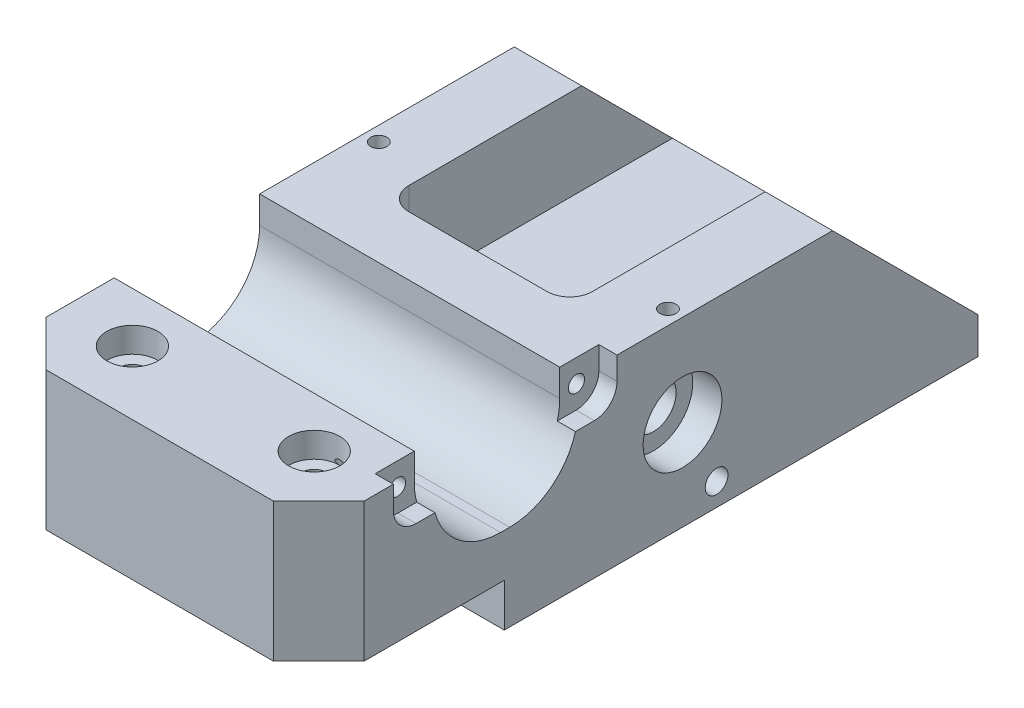
SolidWorks part; units mm, degrees
material "Nylon 6/10"
ref_plane "Front Plane" through (0, 0, 0) normal (0, 0, 1) x (1, 0, 0)
ref_plane "Top Plane" through (0, 0, 0) normal (0, 1, 0) x (1, 0, 0)
ref_plane "Right Plane" through (0, 0, 0) normal (1, 0, 0) x (0, 0, -1)
sketch "Sketch1" plane through (0, 0, 0) normal (0, 1, 0) x (1, 0, 0)
  line L1 (-22.225, -46.0375) -> (22.225, -46.0375)
  line L2 (-22.225, -46.0375) -> (-22.225, 46.0375)
  line L3 (-22.225, 46.0375) -> (22.225, 46.0375)
  line L4 (22.225, -46.0375) -> (22.225, 46.0375)
  line L5 (-22.225, -46.0375) -> (22.225, 46.0375) construction
  line L6 (-22.225, 46.0375) -> (22.225, -46.0375) construction
  point P0 (0, 0)
  dimension "D1" = 44.45
  dimension "D2" = 92.075
extrude "Base" add sketch "Sketch1" along normal blind 12.7 and the other way blind 12.7
sketch "Sketch2" plane through (0, 0, -46.0375) normal (0, 0, -1) x (-1, 0, 0)
  line L1 (-22.225, -12.7) -> (22.225, -12.7) construction
  circle A0 centre (0, -12.7) radius 4.7625
  dimension "D1" = 9.525
extrude "ShaftGuide" cut sketch "Sketch2" against normal blind 41.275
ref_plane "Plane1" through (0, -12.7, 0) normal (0, -1, 0) x (-1, 0, 0)
sketch "Sketch3" plane through (0, -12.7, 0) normal (0, -1, 0) x (-1, 0, 0)
  line L0 (10.922, -20.1295) -> (16.002, -20.1295)
  line L1 (22.225, -46.0375) -> (-22.225, -46.0375) construction
  line L2 (-22.225, -46.0375) -> (-22.225, 46.0375) construction
  line L3 (0, 0) -> (0, 102.0916) construction
  line L5 (-10.922, -20.1295) -> (-10.922, -3.3655)
  line L6 (-22.225, -46.0375) -> (22.225, -46.0375)
  line L7 (-10.922, -3.3655) -> (10.922, -3.3655)
  line L8 (10.922, -20.1295) -> (10.922, -3.3655)
  line L10 (-10.922, -20.1295) -> (-22.225, -20.1295)
  line L11 (-22.225, -46.0375) -> (-22.225, -20.1295)
  line L13 (22.225, -46.0375) -> (22.225, -20.1295)
  line L14 (4.7625, 46.0375) -> (4.7625, 4.7625)
  line L15 (4.7625, 4.7625) -> (-4.7625, 4.7625)
  line L16 (-4.7625, 4.7625) -> (-4.7625, 46.0375)
  line L17 (-4.7625, 46.0375) -> (-22.225, 46.0375)
  line L18 (-22.225, 46.0375) -> (-22.225, -46.0375)
  line L19 (-22.225, -46.0375) -> (22.225, -46.0375)
  line L20 (22.225, -46.0375) -> (22.225, 46.0375)
  line L21 (22.225, 46.0375) -> (4.7625, 46.0375)
  line L23 (22.225, 46.0375) -> (22.225, -46.0375) construction
  line L25 (-4.7625, 46.0375) -> (-22.225, 46.0375) construction
  line L26 (22.225, -20.1295) -> (16.002, -20.1295)
  line L28 (22.225, -46.0375) -> (22.225, 46.0375) construction
  line L29 (22.225, 46.0375) -> (4.7625, 46.0375) construction
  dimension "D6" = 21.844
  dimension "D3" = 49.403
  dimension "D7" = 16.764
  dimension "D1" = 0
extrude "ActuatorPlaneCut" cut sketch "Sketch3" against normal blind 6.0325
sketch "Sketch5" plane through (0, 0, 0) normal (0, 1, 0) x (1, 0, 0)
  line L1 (12.827, 11.1125) -> (-12.827, 11.1125)
  line L2 (12.827, -1.5875) -> (12.827, 11.1125)
  line L3 (12.827, -1.5875) -> (-12.827, -1.5875)
  line L4 (0, 0) -> (0, 121.8983) construction
  line L5 (-10.922, -3.3655) -> (10.922, -3.3655) construction
  line L6 (-12.827, -1.5875) -> (-12.827, 11.1125)
  point P17 (12.827, -1.5875)
  point P20 (12.827, 11.1125)
  dimension "D3" = 1.778
  dimension "D1" = 12.7
  dimension "D2" = 25.654
extrude "CenterSlot" cut sketch "Sketch5" along normal through all and the other way through all
fillet "CenterSlotFillet" radius 3.175 4 edges at (-12.827, 0, -11.1125) (-12.827, 0, 1.5875) (12.827, 0, 1.5875) (12.827, 0, -11.1125)
sketch "Sketch40" plane through (0, -12.7, 0) normal (0, -1, 0) x (1, 0, 0)
  line L1 (10.922, -0.9525) -> (-10.922, -0.9525)
  line L2 (10.922, -0.9525) -> (10.922, 16.9545)
  line L3 (7.747, 20.1295) -> (-7.747, 20.1295)
  line L4 (-10.922, -0.9525) -> (-10.922, 16.9545)
  line L6 (10.922, 3.3655) -> (10.922, 20.1295) construction
  line L7 (-9.652, 1.5875) -> (9.652, 1.5875) construction
  arc A0 (-7.747, 20.1295) -> (-10.922, 16.9545) centre (-7.747, 16.9545) ccw
  arc A1 (7.747, 20.1295) -> (10.922, 16.9545) centre (7.747, 16.9545) cw
  point P8 (-10.922, 20.1295)
  dimension "D1" = 3.175
  dimension "D2" = 2.54
extrude "GearBoxPit" cut sketch "Sketch40" against normal blind 11.176
sketch "Sketch60" plane through (0, 12.7, 0) normal (0, 1, 0) x (1, 0, 0)
  line L0 (22.225, 46.0375) -> (-22.225, 46.0375) construction
  line L1 (-12.827, 7.9375) -> (12.827, 7.9375)
  line L2 (-12.827, 7.9375) -> (-12.827, 46.0375)
  line L3 (-12.827, 46.0375) -> (12.827, 46.0375)
  line L4 (12.827, 7.9375) -> (12.827, 46.0375)
  line L5 (12.827, 1.5875) -> (12.827, 7.9375) construction
extrude "FrontCutaway" cut sketch "Sketch60" against normal blind 12.7
chamfer "ChamferFront" distance 20.32 angle 45 2 edges at (-17.526, 12.7, -46.0375) (17.526, 12.7, -46.0375)
sketch "Sketch67" plane through (0, -12.7, 0) normal (0, -1, 0) x (-1, 0, 0)
  line L0 (-12.3825, -5.3975) -> (12.3825, -5.3975) construction
  line L1 (-12.3825, -5.0006) -> (12.3825, -5.0006)
  line L2 (-12.3825, -5.7944) -> (12.3825, -5.7944)
  line L3 (-12.3825, -16.0655) -> (12.3825, -16.0655) construction
  line L4 (-12.3825, -15.6686) -> (12.3825, -15.6686)
  line L5 (-12.3825, -16.4624) -> (12.3825, -16.4624)
  line L6 (9.652, -1.5875) -> (-9.652, -1.5875) construction
  line L7 (0, 0.0055) -> (0, 0.7987) construction
  arc A0 (-12.3825, -5.0006) -> (-12.3825, -5.7944) centre (-12.3825, -5.3975) ccw
  arc A1 (12.3825, -5.7944) -> (12.3825, -5.0006) centre (12.3825, -5.3975) ccw
  arc A2 (-12.3825, -15.6686) -> (-12.3825, -16.4624) centre (-12.3825, -16.0655) ccw
  arc A3 (12.3825, -16.4624) -> (12.3825, -15.6686) centre (12.3825, -16.0655) ccw
  point P2 (0, -5.3975)
  point P9 (0, -16.0655)
  dimension "D1" = 0.7937
  dimension "D2" = 3.81
  dimension "D3" = 24.765
  dimension "D4" = 10.668
extrude "GearBoxSlotsH" cut sketch "Sketch67" against normal blind 2.286
sketch "Sketch55" plane through (-22.225, 0, 0) normal (-1, 0, 0) x (0, 0, 1)
  line L0 (-46.0375, -12.7) -> (20.1295, -12.7) construction
  line L1 (-11.1125, -12.7) -> (-11.1125, -7.9375) construction
  circle A0 centre (-9.525, -9.525) radius 1.5875
  dimension "D1" = 3.175
  dimension "D2" = 3.175
extrude "GuideBarHole" cut sketch "Sketch55" against normal through all
sketch "Sketch56" plane through (0, 0, 0) normal (1, 0, 0) x (0, 0, -1)
  line L0 (7.9375, -12.7) -> (1.5875, -12.7) construction
  line L1 (7.9375, -12.7) -> (1.5875, -12.7) construction
  line L2 (4.7625, -12.7) -> (4.7625, 12.7) construction
  line L3 (25.7175, 12.7) -> (-46.0375, 12.7) construction
  circle A0 centre (4.7625, 0) radius 3.175
  dimension "D1" = 6.35
extrude "PitchShaftHole" cut sketch "Sketch56" against normal through all and the other way through all
sketch "Sketch57" plane through (-22.225, 0, 0) normal (-1, 0, 0) x (0, 0, 1)
  circle A0 centre (-4.7625, 0) radius 5.5
  circle A1 centre (-4.7625, 0) radius 3.175 construction
  dimension "D1" = 11
extrude "BearingBoreR" cut sketch "Sketch57" against normal blind 4.064
mirror "BearingBoreL" about plane through (0, 0, 0) normal (1, 0, 0) of "BearingBoreR"
hole_wizard "BearingBoreSetScrews" positions "Sketch59" profile "Sketch58" tap size "#4-40" standard "ANSI Inch" end condition up to next
sketch "Sketch59" plane through (4.3433, 12.7, -10.3044) normal (0, 1, 0) x (1, 0, 0)
  line L5 (-26.5683, -0.0419) -> (-26.5683, -11.0419) construction
  line L6 (-26.5683, -0.0419) -> (-26.5683, -11.0419) construction
  line L7 (-26.5683, -5.5419) -> (17.8817, -5.5419) construction
  line L8 (17.8817, -56.3419) -> (17.8817, 15.4131) construction
  line L10 (-26.5683, 15.4131) -> (-26.5683, -56.3419) construction
  point P0 (-24.5363, -5.5419)
  point P2 (15.8497, -5.5419)
  dimension "D1" = 2.032
  dimension "D2" = 2.032
sketch "Sketch58" plane through (-20.193, 12.7, -4.7625) normal (1, 0, 0) x (0, 0, 1)
  line L0 (0, 0) -> (0, 7.2)
  line L1 (0, 7.2) -> (1.1303, 7.2)
  line L2 (1.1303, 7.2) -> (1.1303, 0)
  line L5 (1.1303, 0) -> (0, 0)
  line L11 (0, -6.35) -> (0, 107.95) construction
  dimension "Thru Tap Drill Dia." = 2.2606
  dimension "Thru Tap Drill Depth" = 7.2
cosmetic thread "Hole Thread18" parameters "D2"=2.8448
cosmetic thread "Hole Thread19" parameters "D2"=2.8448
hole_wizard "ToggleAssemHoles" positions "Sketch50" profile "Sketch49" tap size "#6-32" standard "ANSI Inch"
sketch "Sketch50" plane through (0, -12.7, 0) normal (0, -1, 0) x (-1, 0, 0)
  line L1 (4.7625, 46.0375) -> (-4.7625, 46.0375) construction
  line L2 (0, 0) -> (0, 49.3678) construction
  line L3 (-9.652, 11.1125) -> (-4.7625, 11.1125) construction
  point P0 (12.7, 23.8125)
  point P2 (-12.7, 23.8125)
  point P8 (0, 46.0375)
  dimension "D1" = 12.7
  dimension "D2" = 12.7
sketch "Sketch49" plane through (-12.7, -12.7, -23.8125) normal (1, 0, 0) x (0, 0, -1)
  line L0 (0, 0) -> (0, 10.2107)
  line L1 (0, 10.2107) -> (1.3525, 9.398)
  line L2 (1.3525, 9.398) -> (1.3525, 0)
  line L5 (1.3525, 0) -> (0, 0)
  line L10 (0, 10.2107) -> (-1.3526, 9.398) construction
  line L11 (0, -6.35) -> (0, 107.95) construction
  dimension "Tap Drill Dia." = 2.7051
  dimension "Tap Drill Depth" = 9.398
  dimension "Drill Angle" = 118
cosmetic thread "Hole Thread12" parameters "D1"=9.398, "D2"=3.5052
cosmetic thread "Hole Thread13" parameters "D1"=9.398, "D2"=3.5052
chamfer "BackChamfers" distance 6.35 angle 45 2 edges at (22.225, 3.0162, 46.0375) (-22.225, 3.0162, 46.0375)
sketch "Sketch62" plane through (-22.225, 0, 0) normal (-1, 0, 0) x (0, 0, 1)
  line L0 (-46.0375, -12.7) -> (-46.0375, -7.62) construction
  line L1 (-25.7175, 12.7) -> (39.6875, 12.7) construction
  line L2 (9.8425, 9.525) -> (9.8425, 12.7)
  line L3 (30.1625, 9.525) -> (30.1625, 12.7)
  line L4 (30.1625, 12.7) -> (9.8425, 12.7)
  line L5 (9.8425, 9.525) -> (9.8425, 8.89)
  line L6 (19.3675, -0.635) -> (20.6375, -0.635)
  line L7 (30.1625, 8.89) -> (30.1625, 9.525)
  arc A0 (9.8425, 9.525) -> (30.1625, 9.525) centre (20.0025, 9.525) ccw construction
  arc A1 (19.3675, -0.635) -> (9.8425, 8.89) centre (19.3675, 8.89) cw
  arc A2 (20.6375, -0.635) -> (30.1625, 8.89) centre (20.6375, 8.89) ccw
  dimension "D1" = 20.32
  dimension "D4" = 9.525
  dimension "D2" = 66.04
  dimension "D3" = 3.175
extrude "PitchMotorSlot" cut sketch "Sketch62" against normal through all
sketch "Sketch63" plane through (22.225, 0, 0) normal (-1, 0, 0) x (0, 0, 1)
  line L1 (4.3815, 12.7) -> (35.6235, 12.7)
  line L2 (4.3815, 12.7) -> (4.3815, 9.525)
  line L3 (7.5565, 6.35) -> (32.4485, 6.35)
  line L4 (35.6235, 12.7) -> (35.6235, 9.525)
  line L5 (30.1625, 12.7) -> (9.8425, 12.7) construction
  arc A0 (32.4485, 6.35) -> (35.6235, 9.525) centre (32.4485, 9.525) ccw
  arc A1 (7.5565, 6.35) -> (4.3815, 9.525) centre (7.5565, 9.525) cw
  point P4 (20.0025, 12.7)
  dimension "D3" = 3.175
  dimension "D1" = 31.242
  dimension "D2" = 6.35
extrude "PitchMotorMountingSlots" cut sketch "Sketch63" along normal blind 2.54
hole_wizard "PitchMotorMountingHoles" positions "Sketch65" profile "Sketch64" tap size "#4-40" standard "ANSI Inch"
sketch "Sketch65" plane through (19.685, 0, 0) normal (1, 0, 0) x (0, 0, -1)
  line L0 (-35.6235, 12.7) -> (-30.1625, 12.7) construction
  line L3 (-30.1625, 12.7) -> (-9.8425, 12.7) construction
  line L5 (-20.0025, 12.7) -> (-20.0025, 7.4827) construction
  point P0 (-32.4993, 9.525)
  point P2 (-7.5057, 9.525)
  dimension "D1" = 3.175
  dimension "D2" = 24.9936
sketch "Sketch64" plane through (19.685, 9.525, 32.4993) normal (0, 1, 0) x (0, 0, -1)
  line L0 (0, 0) -> (0, 8.2738)
  line L1 (0, 8.2738) -> (1.1303, 7.5946)
  line L2 (1.1303, 7.5946) -> (1.1303, 0)
  line L5 (1.1303, 0) -> (0, 0)
  line L10 (0, 8.2738) -> (-1.1303, 7.5946) construction
  line L11 (0, -6.35) -> (0, 107.95) construction
  dimension "Tap Drill Dia." = 2.2606
  dimension "Tap Drill Depth" = 7.5946
  dimension "Drill Angle" = 118
cosmetic thread "Hole Thread20" parameters "D1"=7.5946, "D2"=2.8448
cosmetic thread "Hole Thread21" parameters "D1"=7.5946, "D2"=2.8448
hole_wizard "GearBoxMountingHoles" positions "Sketch69" profile "Sketch68" tap size "#6-32" standard "ANSI Inch"
sketch "Sketch69" plane through (0, -12.7, 0) normal (0, -1, 0) x (-1, 0, 0)
  line L0 (-12.3825, -5.7944) -> (-10.922, -5.7944) construction
  line L1 (-10.922, -15.6686) -> (-12.3825, -15.6686) construction
  line L2 (-22.225, -5.7944) -> (-10.922, -5.7944) construction
  line L3 (-10.922, -15.6686) -> (-22.225, -15.6686) construction
  line L4 (-16.5735, -15.6686) -> (-16.5735, -5.7944) construction
  line L6 (0, 0) -> (0, 15.1935) construction
  line L9 (-22.225, -20.1295) -> (-22.225, 46.0375) construction
  line L10 (10.922, -5.7944) -> (22.225, -5.7944) construction
  line L11 (22.225, 46.0375) -> (22.225, -20.1295) construction
  line L13 (10.922, -15.6686) -> (22.225, -15.6686) construction
  line L14 (12.3825, -15.6686) -> (10.922, -15.6686) construction
  line L15 (10.922, -15.6686) -> (10.922, -5.7944) construction
  line L17 (16.5735, -15.6686) -> (16.5735, -5.7944) construction
  point P0 (-16.5735, -10.7315)
  point P2 (16.5735, -10.7315)
sketch "Sketch68" plane through (16.5735, -12.7, 10.7315) normal (1, 0, 0) x (0, 0, -1)
  line L0 (0, 0) -> (0, 10.2107)
  line L1 (0, 10.2107) -> (1.3525, 9.398)
  line L2 (1.3525, 9.398) -> (1.3525, 0)
  line L5 (1.3525, 0) -> (0, 0)
  line L10 (0, 10.2107) -> (-1.3526, 9.398) construction
  line L11 (0, -6.35) -> (0, 107.95) construction
  dimension "Tap Drill Dia." = 2.7051
  dimension "Tap Drill Depth" = 9.398
  dimension "Drill Angle" = 118
hole_wizard "CapMountingHoles" positions "Sketch74" profile "Sketch73" counterbore size "#6" standard "ANSI Inch" end condition through all
sketch "Sketch74" plane through (-0.8379, 12.7, 8.6337) normal (0, -1, 0) x (-1, 0, 0)
  line L8 (-0.8379, -1002.5128) -> (-0.8379, 48997.4872) construction
  line L9 (15.0371, -37.4038) -> (-16.7129, -37.4038) construction
  point P0 (-13.5379, -28.5138)
  point P2 (11.8621, -28.5138)
  dimension "D1" = 25.4
  dimension "D2" = 8.89
sketch "Sketch73" plane through (12.7, 12.7, 37.1475) normal (1, 0, 0) x (0, 0, 1)
  line L0 (0, 0) -> (0, 25.4)
  line L1 (0, 25.4) -> (1.8288, 25.4)
  line L3 (1.8288, 25.4) -> (1.8288, 3.5052)
  line L4 (1.8288, 3.5052) -> (3.5725, 3.5052)
  line L5 (3.5725, 3.5052) -> (3.5725, 0)
  line L7 (3.5725, 0) -> (0, 0)
  line L11 (0, -6.35) -> (0, 107.95) construction
  dimension "Thru Hole Dia." = 3.6576
  dimension "Thru Hole Depth" = 25.4
  dimension "C'Bore Dia." = 7.145
  dimension "C'Bore Depth" = 3.5052
